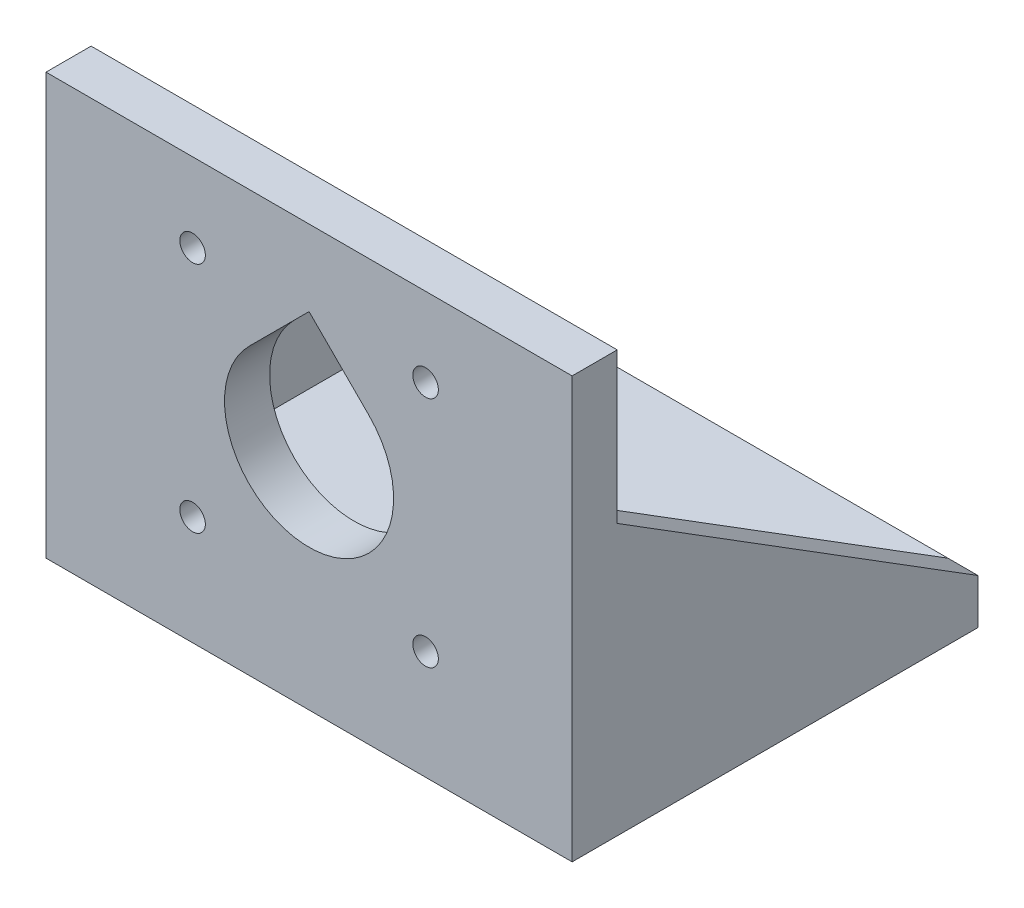
SolidWorks part; units mm, degrees
ref_plane "Спереди" through (0, 0, 0) normal (0, 0, 1) x (1, 0, 0)
ref_plane "Сверху" through (0, 0, 0) normal (0, 1, 0) x (1, 0, 0)
ref_plane "Справа" through (0, 0, 0) normal (1, 0, 0) x (0, 0, -1)
other "Configuration Table"
sketch "01_Пластина_эскиз" plane through (0, 0, 0) normal (0, 0, 1) x (1, 0, 0)
  line L1 (0, 0) -> (70, 0)
  line L2 (0, 0) -> (0, 56)
  line L3 (0, 56) -> (70, 56)
  line L4 (70, 0) -> (70, 56)
  dimension "D1" = 70
  dimension "D2" = 56
extrude "01_Передняя_пластина" add sketch "01_Пластина_эскиз" along normal blind 6
sketch "02_Полка_эскиз" plane through (0, 0, 0) normal (0, 1, 0) x (1, 0, 0)
  line L1 (0, 48) -> (70, 48)
  line L2 (0, 48) -> (0, -6)
  line L3 (0, -6) -> (70, -6)
  line L4 (70, 48) -> (70, -6)
  dimension "D1" = 70
  dimension "D2" = 54
  dimension "D3" = 6
extrude "02_Полка" add sketch "02_Полка_эскиз" along normal blind 6
sketch "03_Косынка_левая_эскиз" plane through (0, 0, 0) normal (1, 0, 0) x (0, 0, -1)
  line L0 (48, 6) -> (0, 6)
  line L1 (0, 6) -> (0, 36)
  line L2 (0, 36) -> (48, 6)
  dimension "D3" = 6
  dimension "D1" = 48
  dimension "D2" = 30
extrude "03_Косынка_левая" add sketch "03_Косынка_левая_эскиз" along normal blind 4
sketch "04_Косынка_правая_эскиз" plane through (0, 0, 0) normal (1, 0, 0) x (0, 0, -1)
  line L0 (48, 6) -> (0, 6)
  line L1 (0, 6) -> (0, 36)
  line L2 (0, 36) -> (48, 6)
  dimension "D3" = 6
  dimension "D1" = 48
  dimension "D2" = 30
extrude "04_Косынка_правая" add sketch "04_Косынка_правая_эскиз" along normal blind 4 from offset 66
sketch "05_Мотор_передний_фланец_эскиз" plane through (0, 0, 0) normal (0, 0, 1) x (1, 0, 0)
  circle A0 centre (35, 30) radius 11.25
  circle A1 centre (19.5, 14.5) radius 1.7
  circle A2 centre (19.5, 45.5) radius 1.7
  circle A3 centre (50.5, 14.5) radius 1.7
  circle A4 centre (50.5, 45.5) radius 1.7
  dimension "D1" = 3.4
  dimension "D2" = 3.4
  dimension "D3" = 3.4
  dimension "D4" = 3.4
  dimension "D5" = 22.5
  dimension "D6" = 15.5
  dimension "D7" = 31
  dimension "D8" = 15.5
  dimension "D9" = 31
  dimension "D10" = 35
  dimension "D11" = 30
extrude "05_Буртик_и_4_отверстия_М3" cut sketch "05_Мотор_передний_фланец_эскиз" against normal through all and the other way through all
sketch "06_Свод_45град_эскиз" plane through (0, 0, 0) normal (0, 0, 1) x (1, 0, 0)
  line L0 (27.045, 37.955) -> (42.955, 37.955)
  line L1 (42.955, 37.955) -> (35, 45.9099)
  line L2 (35, 45.9099) -> (27.045, 37.955)
  dimension "D1" = 7.955
  dimension "D2" = 15.9099
  dimension "D3" = 7.955
  dimension "D4" = 35
  dimension "D5" = 45.9099
extrude "06_Свод_отверстия_для_печати" cut sketch "06_Свод_45град_эскиз" against normal through all and the other way through all
sketch "07_Крепление_полки_эскиз" plane through (0, 0, 0) normal (0, 1, 0) x (1, 0, 0)
  circle A0 centre (8.5, 12) radius 2.25
  circle A1 centre (8.5, 38) radius 2.25
  circle A2 centre (61.5, 12) radius 2.25
  circle A3 centre (61.5, 38) radius 2.25
  dimension "D1" = 4.5
  dimension "D2" = 4.5
  dimension "D3" = 4.5
  dimension "D4" = 4.5
  dimension "D5" = 53
  dimension "D6" = 26
  dimension "D7" = 8.5
  dimension "D8" = 12
extrude "07_4_отверстия_М4" cut sketch "07_Крепление_полки_эскиз" against normal through all and the other way through all
equation "\"Ширина\"= 70"
equation "\"Высота пластины\"= 56"
equation "\"Толщина стенок\"= 6"
equation "\"Длина полки\"= 48"
equation "\"Толщина косынки\"= 4"
equation "\"Высота косынки\"= 30"
equation "\"Высота оси\"= 30"
equation "\"Шаг М3 ПРЕДВ\"= 31"
equation "\"Отверстие буртика\"= 22.5"
equation "\"Отверстия М3\"= 3.4"
equation "\"Отверстия М4\"= 4.5"
equation "\"Отступ М4 сбоку\"= 8.5"
equation "\"Ближний ряд М4\"= 12"
equation "\"Отступ М4 сзади\"= 10"
equation "\"D1@01_Пластина_эскиз\" = \"Ширина\""
equation "\"D2@01_Пластина_эскиз\" = \"Высота пластины\""
equation "\"D1@01_Передняя_пластина\" = \"Толщина стенок\""
equation "\"D1@02_Полка_эскиз\" = \"Ширина\""
equation "\"D2@02_Полка_эскиз\" = \"Длина полки\" + \"Толщина стенок\""
equation "\"D1@02_Полка\" = \"Толщина стенок\""
equation "\"D1@03_Косынка_левая_эскиз\" = \"Длина полки\""
equation "\"D2@03_Косынка_левая_эскиз\" = \"Высота косынки\""
equation "\"D1@03_Косынка_левая\" = \"Толщина косынки\""
equation "\"D1@04_Косынка_правая_эскиз\" = \"Длина полки\""
equation "\"D2@04_Косынка_правая_эскиз\" = \"Высота косынки\""
equation "\"D1@04_Косынка_правая\" = \"Толщина косынки\""
equation "\"D19@04_Косынка_правая\" = \"Ширина\" - \"Толщина косынки\""
equation "\"D1@05_Мотор_передний_фланец_эскиз\" = \"Отверстия М3\""
equation "\"D2@05_Мотор_передний_фланец_эскиз\" = \"Отверстия М3\""
equation "\"D3@05_Мотор_передний_фланец_эскиз\" = \"Отверстия М3\""
equation "\"D4@05_Мотор_передний_фланец_эскиз\" = \"Отверстия М3\""
equation "\"D5@05_Мотор_передний_фланец_эскиз\" = \"Отверстие буртика\""
equation "\"D6@05_Мотор_передний_фланец_эскиз\" = \"Шаг М3 ПРЕДВ\" / 2"
equation "\"D7@05_Мотор_передний_фланец_эскиз\" = \"Шаг М3 ПРЕДВ\""
equation "\"D8@05_Мотор_передний_фланец_эскиз\" = \"Шаг М3 ПРЕДВ\" / 2"
equation "\"D9@05_Мотор_передний_фланец_эскиз\" = \"Шаг М3 ПРЕДВ\""
equation "\"D1@06_Свод_45град_эскиз\" = \"Отверстие буртика\" / (2 * SQR(2))"
equation "\"D2@06_Свод_45град_эскиз\" = \"Отверстие буртика\" / SQR(2)"
equation "\"D3@06_Свод_45град_эскиз\" = \"Отверстие буртика\" / (2 * SQR(2))"
equation "\"D1@07_Крепление_полки_эскиз\" = \"Отверстия М4\""
equation "\"D2@07_Крепление_полки_эскиз\" = \"Отверстия М4\""
equation "\"D3@07_Крепление_полки_эскиз\" = \"Отверстия М4\""
equation "\"D4@07_Крепление_полки_эскиз\" = \"Отверстия М4\""
equation "\"D5@07_Крепление_полки_эскиз\" = \"Ширина\" - 2 * \"Отступ М4 сбоку\""
equation "\"D6@07_Крепление_полки_эскиз\" = \"Длина полки\" - \"Ближний ряд М4\" - \"Отступ М4 сзади\""
equation "\"D3@02_Полка_эскиз\" = \"Толщина стенок\""
equation "\"D3@03_Косынка_левая_эскиз\" = \"Толщина стенок\""
equation "\"D3@04_Косынка_правая_эскиз\" = \"Толщина стенок\""
equation "\"D10@05_Мотор_передний_фланец_эскиз\" = \"Ширина\" / 2"
equation "\"D11@05_Мотор_передний_фланец_эскиз\" = \"Высота оси\""
equation "\"D4@06_Свод_45град_эскиз\" = \"Ширина\" / 2"
equation "\"D5@06_Свод_45град_эскиз\" = \"Высота оси\" + \"Отверстие буртика\" / SQR(2)"
equation "\"D7@07_Крепление_полки_эскиз\" = \"Отступ М4 сбоку\""
equation "\"D8@07_Крепление_полки_эскиз\" = \"Ближний ряд М4\""
